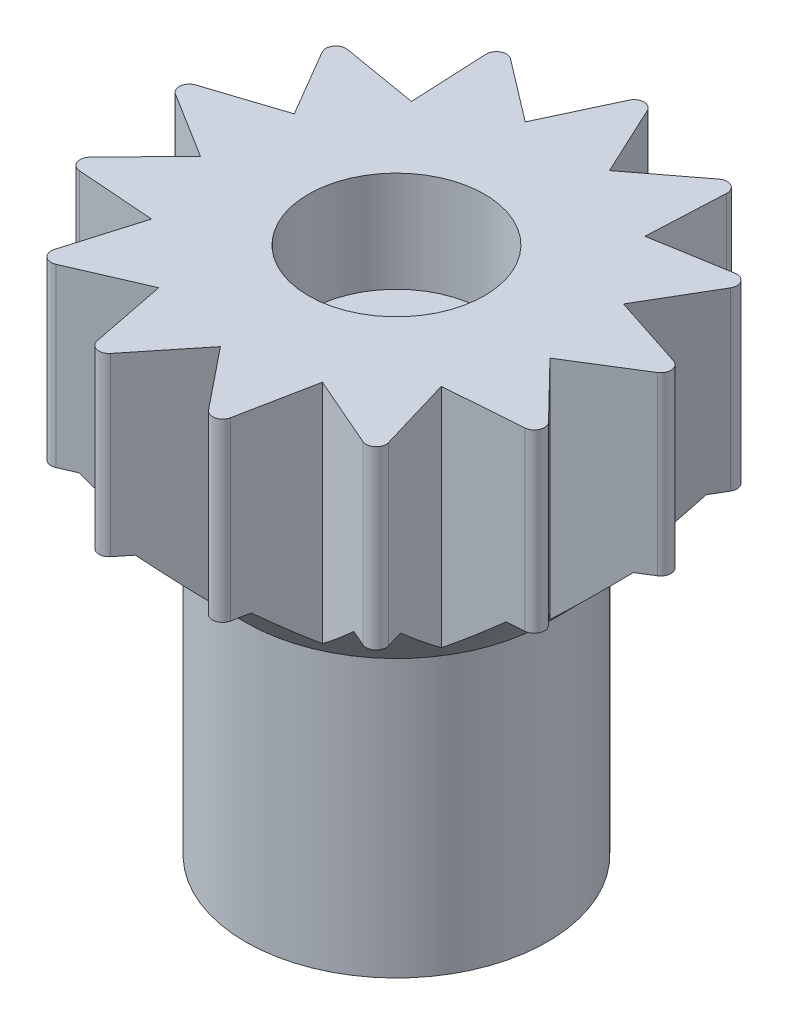
SolidWorks part; units mm, degrees
ref_plane "Front" through (0, 0, 0) normal (0, 0, 1) x (1, 0, 0)
ref_plane "Top" through (0, 0, 0) normal (0, 1, 0) x (1, 0, 0)
ref_plane "Right" through (0, 0, 0) normal (1, 0, 0) x (0, 0, -1)
sketch "Sketch1" plane through (0, 0, 0) normal (0, 1, 0) x (1, 0, 0)
  line L0 (2.3209, 2.6198) -> (4.275, 2.9508)
  line L1 (4.275, 2.9508) -> (3.2726, 1.2411)
  line L2 (3.2726, 1.2411) -> (5.1567, 0.6261)
  line L3 (5.1567, 0.6261) -> (3.4745, -0.4219)
  line L4 (3.4745, -0.4219) -> (4.857, -1.842)
  line L5 (4.857, -1.842) -> (2.8804, -1.9882)
  line L6 (2.8804, -1.9882) -> (3.4446, -3.8882)
  line L7 (3.4446, -3.8882) -> (1.6265, -3.0991)
  line L8 (1.6265, -3.0991) -> (1.2431, -5.0436)
  line L9 (1.2431, -5.0436) -> (0, -3.5)
  line L10 (0, -3.5) -> (-1.2431, -5.0436)
  line L11 (-1.2431, -5.0436) -> (-1.6265, -3.0991)
  line L12 (-1.6265, -3.0991) -> (-3.4446, -3.8882)
  line L13 (-3.4446, -3.8882) -> (-2.8804, -1.9882)
  line L14 (-2.8804, -1.9882) -> (-4.857, -1.842)
  line L15 (-4.857, -1.842) -> (-3.4745, -0.4219)
  line L16 (-3.4745, -0.4219) -> (-5.1567, 0.6261)
  line L17 (-5.1567, 0.6261) -> (-3.2726, 1.2411)
  line L18 (-3.2726, 1.2411) -> (-4.275, 2.9508)
  line L19 (-4.275, 2.9508) -> (-2.3209, 2.6198)
  line L20 (-2.3209, 2.6198) -> (-2.414, 4.5995)
  line L21 (-2.414, 4.5995) -> (-0.8376, 3.3983)
  line L22 (-0.8376, 3.3983) -> (0, 5.1945)
  line L23 (0, 5.1945) -> (0.8376, 3.3983)
  line L24 (0.8376, 3.3983) -> (2.414, 4.5995)
  line L25 (2.414, 4.5995) -> (2.3209, 2.6198)
  line L26 (-0.8376, 3.3983) -> (0.8376, 3.3983) construction
  circle A0 centre (0, 0) radius 3.5 construction
  circle A1 centre (0, 0) radius 0.5
  circle A2 centre (0, 0) radius 5.1945 construction
  point P44 (0, 0)
  dimension "D2" = 7
  dimension "D4" = 1
  dimension "D7" = 10.3891
  dimension "D3" = 50
  dimension "D5" = 1.6752
  dimension "D6" = 1.7962
  dimension "D1" = 13
extrude "Boss-Extrude1" add sketch "Sketch1" along normal blind 3.5
sketch "Sketch3" plane through (0, 0, 0) normal (0, -1, 0) x (1, 0, 0)
  circle A0 centre (0, 0) radius 3
  circle A1 centre (0, 0) radius 0.5
  dimension "D1" = 6
extrude "Boss-Extrude2" add sketch "Sketch3" along normal blind 7
sketch "Sketch2" plane through (0, -7, 0) normal (0, -1, 0) x (1, 0, 0)
  line L0 (-1.5593, -0.7945) -> (-2.0448, -0.6644)
  line L1 (-2.0448, -0.6644) -> (-1.7285, -0.2738)
  line L2 (-1.7285, -0.2738) -> (-2.15, 0)
  line L3 (-2.15, 0) -> (-1.7285, 0.2738)
  line L4 (-1.7285, 0.2738) -> (-2.0448, 0.6644)
  line L5 (-2.0448, 0.6644) -> (-1.5593, 0.7945)
  line L6 (-1.5593, 0.7945) -> (-1.7394, 1.2637)
  line L7 (-1.7394, 1.2637) -> (-1.2374, 1.2374)
  line L8 (-1.2374, 1.2374) -> (-1.2637, 1.7394)
  line L9 (-1.2637, 1.7394) -> (-0.7945, 1.5593)
  line L10 (-0.7945, 1.5593) -> (-0.6644, 2.0448)
  line L11 (-0.6644, 2.0448) -> (-0.2738, 1.7285)
  line L12 (-0.2738, 1.7285) -> (0, 2.15)
  line L13 (0, 2.15) -> (0.2738, 1.7285)
  line L14 (0.2738, 1.7285) -> (0.6644, 2.0448)
  line L15 (0.6644, 2.0448) -> (0.7945, 1.5593)
  line L16 (0.7945, 1.5593) -> (1.2637, 1.7394)
  line L17 (1.2637, 1.7394) -> (1.2374, 1.2374)
  line L18 (1.2374, 1.2374) -> (1.7394, 1.2637)
  line L19 (1.7394, 1.2637) -> (1.5593, 0.7945)
  line L20 (1.5593, 0.7945) -> (2.0448, 0.6644)
  line L21 (2.0448, 0.6644) -> (1.7285, 0.2738)
  line L22 (1.7285, 0.2738) -> (2.15, 0)
  line L23 (2.15, 0) -> (1.7285, -0.2738)
  line L24 (1.7285, -0.2738) -> (2.0448, -0.6644)
  line L25 (2.0448, -0.6644) -> (1.5593, -0.7945)
  line L26 (1.5593, -0.7945) -> (1.7394, -1.2637)
  line L36 (-0.7945, -1.5593) -> (-1.2637, -1.7394)
  line L37 (-1.2637, -1.7394) -> (-1.2374, -1.2374)
  line L38 (-1.2374, -1.2374) -> (-1.7394, -1.2637)
  line L39 (-1.7394, -1.2637) -> (-1.5593, -0.7945)
  line L40 (1.7394, -1.2637) -> (1.2374, -1.2374)
  line L41 (1.2374, -1.2374) -> (1.2637, -1.7394)
  line L42 (1.2637, -1.7394) -> (0.7945, -1.5593)
  line L43 (0.7945, -1.5593) -> (0.6644, -2.0448)
  line L44 (0.6644, -2.0448) -> (0.2738, -1.7285)
  line L45 (0.2738, -1.7285) -> (0, -2.15)
  line L46 (0, -2.15) -> (-0.2738, -1.7285)
  line L47 (-0.2738, -1.7285) -> (-0.6644, -2.0448)
  line L48 (-0.6644, -2.0448) -> (-0.7945, -1.5593)
  circle A0 centre (0, 0) radius 1.75 construction
  circle A1 centre (0, 0) radius 2.15 construction
  dimension "D1" = 3.5
  dimension "D2" = 4.3
extrude "Cut-Extrude1" cut sketch "Sketch2" against normal blind 4
fillet "Fillet1" radius 0.2 13 edges at (-5.1567, 1.75, -0.6261) (-4.857, 1.75, 1.842) (-3.4446, 1.75, 3.8882) (-1.2431, 1.75, 5.0436) (1.2431, 1.75, 5.0436) (3.4446, 1.75, 3.8882) (4.857, 1.75, 1.842) (5.1567, 1.75, -0.6261) (4.275, 1.75, -2.9508) (2.414, 1.75, -4.5995) (0, 1.75, -5.1945) (-2.414, 1.75, -4.5995) (-4.275, 1.75, -2.9508)
chamfer "Chamfer1" distance 1.5 angle 45 1 edges at (0, 0, -3)
sketch "Sketch4" plane through (0, 3.5, 0) normal (0, 1, 0) x (1, 0, 0)
  circle A0 centre (0, 0) radius 1.75
  dimension "D1" = 3.5
extrude "Cut-Extrude2" cut sketch "Sketch4" against normal blind 2
